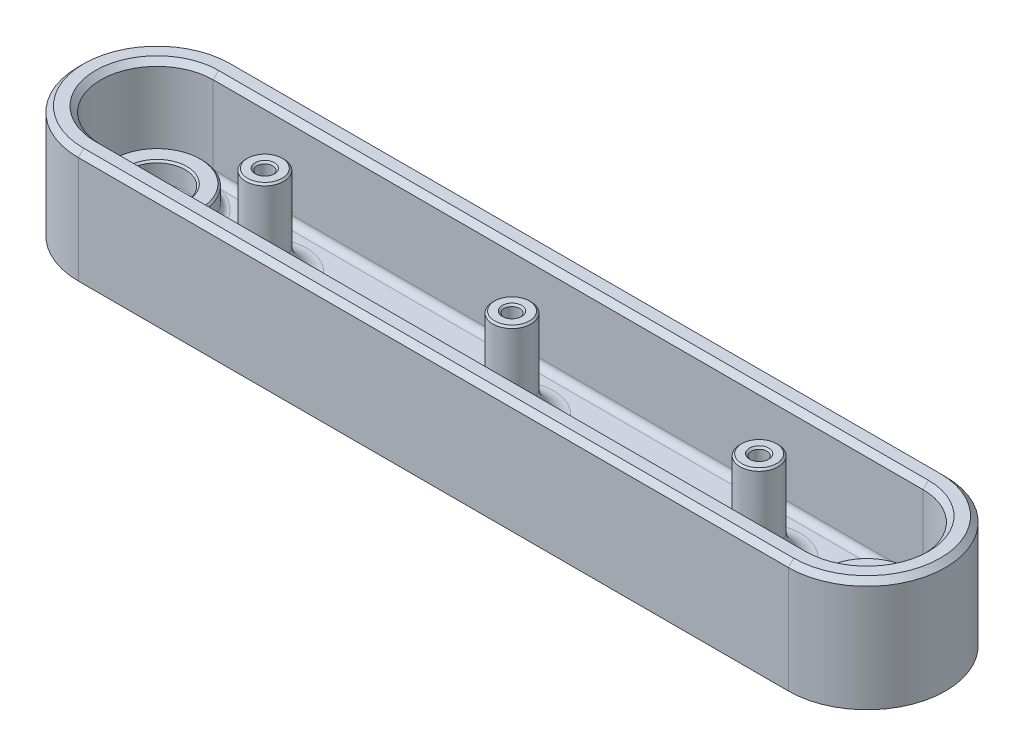
SolidWorks part; units mm, degrees
material "PLA"
ref_plane "Front Plane" through (0, 0, 0) normal (0, 0, 1) x (1, 0, 0)
ref_plane "Top Plane" through (0, 0, 0) normal (0, 1, 0) x (1, 0, 0)
ref_plane "Right Plane" through (0, 0, 0) normal (1, 0, 0) x (0, 0, -1)
sketch "Sketch1" plane through (0, 0, 0) normal (0, 1, 0) x (1, 0, 0)
  line L0 (-100.33, 0) -> (100.33, 0) construction
  line L1 (0, -55.9739) -> (0, 55.9739) construction
  line L2 (-100.33, 22.225) -> (100.33, 22.225)
  line L3 (-100.33, -22.225) -> (100.33, -22.225)
  arc A0 (-100.33, 22.225) -> (-100.33, -22.225) centre (-100.33, 0) ccw
  arc A1 (100.33, 22.225) -> (100.33, -22.225) centre (100.33, 0) cw
  point P4 (0, 0)
  point P10 (0, 0)
  dimension "D2" = 44.45
  dimension "D1" = 200.66
extrude "MainBlock" add sketch "Sketch1" along normal blind 31.75
sketch "Sketch2" plane through (0, 31.75, 0) normal (0, 1, 0) x (1, 0, 0)
  line L0 (0, 0) -> (155.7407, 0) construction
  line L1 (0, 0) -> (0, 57.4416) construction
  line L2 (-100.33, -22.225) -> (100.33, -22.225) construction
  line L3 (100.33, 22.225) -> (-100.33, 22.225) construction
  line L4 (-100.33, -22.225) -> (100.33, -22.225) construction
  line L5 (100.33, 22.225) -> (-100.33, 22.225) construction
  line L6 (-100.33, 15.875) -> (100.33, 15.875)
  line L7 (-100.33, -15.875) -> (100.33, -15.875)
  arc A0 (100.33, -22.225) -> (100.33, 22.225) centre (100.33, 0) ccw construction
  arc A1 (-100.33, 22.225) -> (-100.33, -22.225) centre (-100.33, 0) ccw construction
  arc A2 (100.33, -22.225) -> (100.33, 22.225) centre (100.33, 0) ccw construction
  arc A3 (-100.33, 22.225) -> (-100.33, -22.225) centre (-100.33, 0) ccw construction
  arc A4 (-100.33, 15.875) -> (-100.33, -15.875) centre (-100.33, 0) ccw
  arc A5 (100.33, 15.875) -> (100.33, -15.875) centre (100.33, 0) cw
  point P18 (0, 15.875)
  point P19 (0, -15.875)
  dimension "D1" = 6.35
extrude "MainPocket" cut sketch "Sketch2" against normal blind 25.4
sketch "Sketch3" plane through (0, 0, 0) normal (0, -1, 0) x (1, 0, 0)
  line L2 (-100.33, -22.225) -> (100.33, -22.225)
  line L3 (100.33, 22.225) -> (-100.33, 22.225)
  line L4 (-100.33, -22.225) -> (100.33, -22.225) construction
  line L5 (100.33, 22.225) -> (-100.33, 22.225) construction
  circle A0 centre (-100.33, 0) radius 4.445
  circle A1 centre (100.33, 0) radius 4.445
  arc A2 (-100.33, 22.225) -> (-100.33, -22.225) centre (-100.33, 0) ccw
  arc A3 (100.33, -22.225) -> (100.33, 22.225) centre (100.33, 0) ccw
  arc A4 (-100.33, 22.225) -> (-100.33, -22.225) centre (-100.33, 0) ccw construction
  arc A5 (100.33, -22.225) -> (100.33, 22.225) centre (100.33, 0) ccw construction
  dimension "D2" = 8.89
  dimension "D3" = 8.89
  dimension "D1" = 0
extrude "Cut-Extrude1" cut sketch "Sketch3" against normal through all
sketch "Sketch4" plane through (0, 6.35, 0) normal (0, 1, 0) x (1, 0, 0)
  line L0 (0, 0) -> (50000, 0) construction
  line L1 (0, 0) -> (0, 50000) construction
  line L2 (100.33, 15.875) -> (-100.33, 15.875)
  line L3 (-100.33, -15.875) -> (100.33, -15.875)
  line L4 (100.33, 15.875) -> (-100.33, 15.875) construction
  line L5 (-100.33, -15.875) -> (100.33, -15.875) construction
  circle A0 centre (-100.33, 0) radius 7.9566
  circle A1 centre (-100.33, 0) radius 12.7
  arc A2 (100.33, -15.875) -> (100.33, 15.875) centre (100.33, 0) ccw
  arc A3 (-100.33, 15.875) -> (-100.33, -15.875) centre (-100.33, 0) ccw
  arc A4 (100.33, -15.875) -> (100.33, 15.875) centre (100.33, 0) ccw construction
  arc A5 (-100.33, 15.875) -> (-100.33, -15.875) centre (-100.33, 0) ccw construction
  circle A6 centre (100.33, 0) radius 12.7
  circle A7 centre (100.33, 0) radius 7.9566
  dimension "D2" = 15.9131
  dimension "D3" = 25.4
  dimension "D1" = 0
extrude "Boss-Extrude1" add sketch "Sketch4" along normal blind 6.35
sketch "Sketch5" plane through (0, 0, 0) normal (0, -1, 0) x (1, 0, 0)
  line L0 (0, 0) -> (0, 50000) construction
  line L2 (-100.33, -22.225) -> (100.33, -22.225)
  line L3 (100.33, 22.225) -> (-100.33, 22.225)
  line L4 (-100.33, -22.225) -> (100.33, -22.225) construction
  line L5 (100.33, 22.225) -> (-100.33, 22.225) construction
  circle A0 centre (-100.33, 0) radius 6.35
  circle A1 centre (-100.33, 0) radius 4.445 construction
  arc A2 (-100.33, 22.225) -> (-100.33, -22.225) centre (-100.33, 0) ccw
  arc A3 (100.33, -22.225) -> (100.33, 22.225) centre (100.33, 0) ccw
  arc A4 (-100.33, 22.225) -> (-100.33, -22.225) centre (-100.33, 0) ccw construction
  arc A5 (100.33, -22.225) -> (100.33, 22.225) centre (100.33, 0) ccw construction
  circle A6 centre (-100.33, 0) radius 4.445
  circle A7 centre (100.33, 0) radius 4.445 construction
  circle A8 centre (100.33, 0) radius 6.35 construction
  dimension "D2" = 12.7
  dimension "D1" = 0
extrude "Boss-Extrude2" [suppressed] add sketch "Sketch5" along normal blind 3.81
fillet "Fillet1" [suppressed] radius 1.27
sketch "Sketch7" plane through (0, 6.35, 0) normal (0, 1, 0) x (1, 0, 0)
  line L0 (1.3556, 0) -> (50001.3556, 0) construction
  circle A0 centre (0, 0) radius 2.2225
  circle A1 centre (-69.85, 0) radius 2.2225
  circle A2 centre (-100.33, 0) radius 4.445 construction
  circle A3 centre (100.33, 0) radius 4.445 construction
  circle A4 centre (100.33, 0) radius 4.445 construction
  circle A5 centre (-100.33, 0) radius 4.445 construction
  circle A6 centre (69.85, 0) radius 2.2225
  circle A7 centre (-69.85, 0) radius 5.3975
  circle A8 centre (0, 0) radius 5.3975
  circle A9 centre (69.85, 0) radius 5.3975
  dimension "D3" = 4.445
  dimension "D4" = 4.445
  dimension "D5" = 4.445
  dimension "D6" = 10.795
  dimension "D7" = 10.795
  dimension "D8" = 10.795
  dimension "D1" = 30.48
  dimension "D2" = 30.48
extrude "Boss-Extrude3" add sketch "Sketch7" along normal up to surface (25.4 mm away) up to face at (0, 31.75, 0)
fillet "Fillet2" radius 0.635 2 edges at (100.33, 6.35, -7.9566) (-100.33, 6.35, 7.9566)
fillet "Fillet3" radius 1.905 6 edges at (116.205, 6.35, 0) (0, 6.35, 15.875) (-116.205, 6.35, 0) (100.33, 6.35, -12.7) (-100.33, 6.35, -12.7) (0, 6.35, -15.875)
fillet "Fillet6" radius 6.35 3 edges at (69.85, 6.35, -5.3975) (0, 6.35, -5.3975) (-69.85, 6.35, -5.3975)
sketch "Sketch9" plane through (0, 0, 0) normal (0, -1, 0) x (1, 0, 0)
  circle A0 centre (100.33, 0) radius 4.445 construction
  circle A1 centre (100.33, 0) radius 4.445
  circle A6 centre (100.33, 0) radius 5.715
  dimension "D2" = 11.43
extrude "Bearing-Spacer" [suppressed] add sketch "Sketch9" along normal blind 8.89
fillet "Fillet7" [suppressed] radius 2.54
chamfer "Chamfer1" [suppressed] distance 0.508 angle 45
chamfer "Chamfer2" distance 0.508 angle 45 12 edges at (69.85, 31.75, 2.2225) (100.33, 6.35, -4.445) (100.33, 12.7, -12.7) (100.33, 12.7, -7.9566) (-100.33, 6.35, -4.445) (-100.33, 12.7, 12.7) (-69.85, 31.75, 5.3975) (0, 31.75, 5.3975) (0, 31.75, 2.2225) (69.85, 31.75, 5.3975) (-100.33, 12.7, 7.9566) (-69.85, 31.75, 2.2225)
chamfer "Chamfer3" distance 1.524 angle 45 8 edges at (0, 31.75, -22.225) (-122.555, 31.75, 0) (122.555, 31.75, 0) (0, 31.75, 22.225) (0, 31.75, -15.875) (-116.205, 31.75, 0) (116.205, 31.75, 0) (0, 31.75, 15.875)
chamfer "Chamfer5" [suppressed] distance 0.381 angle 45
sketch "Sketch10" plane through (0, 6.35, 0) normal (0, 1, 0) x (1, 0, 0)
  circle A0 centre (69.85, 0) radius 2.2225 construction
  circle A1 centre (0, 0) radius 2.2225 construction
  circle A2 centre (-69.85, 0) radius 2.2225 construction
  circle A3 centre (69.85, 0) radius 2.2225
  circle A4 centre (0, 0) radius 2.2225
  circle A5 centre (-69.85, 0) radius 2.2225
extrude "Boss-Extrude4" add sketch "Sketch10" along normal blind 16.51
equation "\"D5@Sketch7\"=\"D3@Sketch7\""
equation "\"D4@Sketch7\"=\"D3@Sketch7\""
equation "\"D7@Sketch7\"=\"D6@Sketch7\""
equation "\"D8@Sketch7\"=\"D6@Sketch7\""
